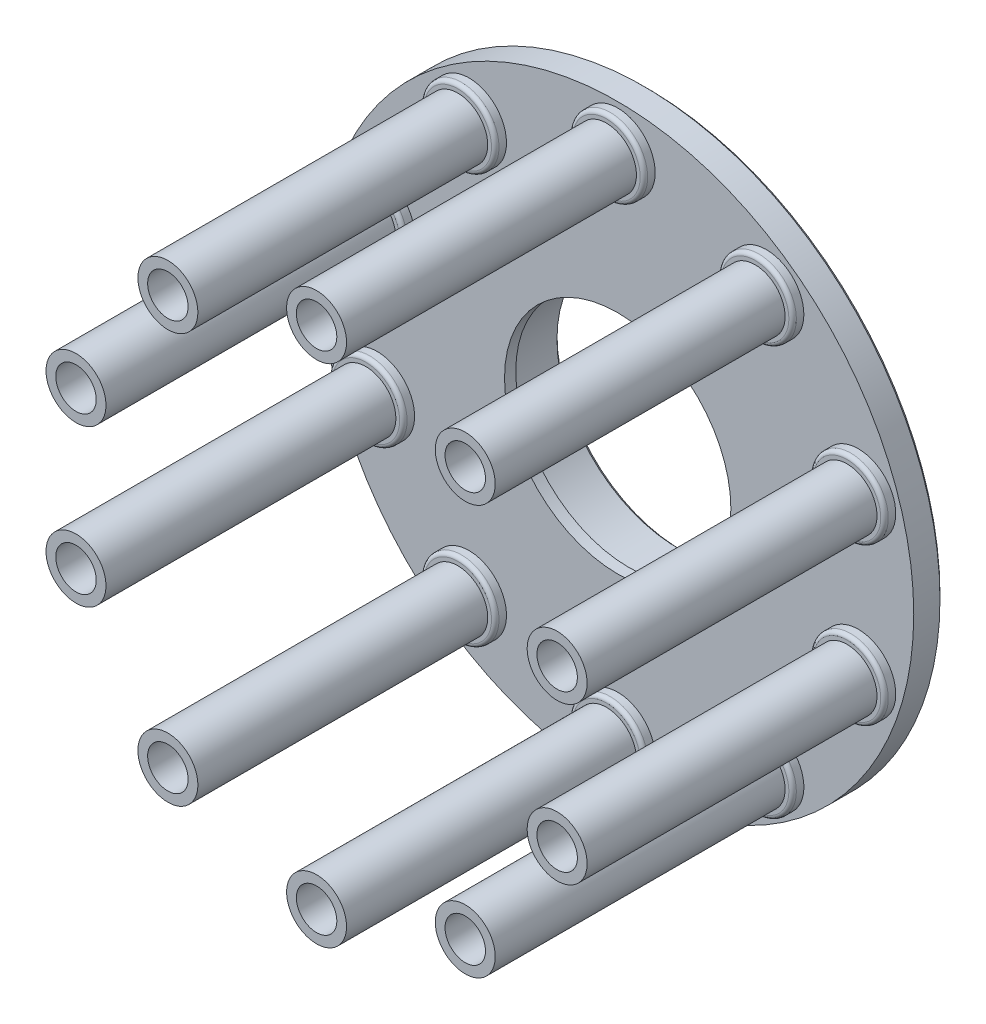
SolidWorks part; units mm, degrees
material "PLA"
ref_plane "Front Plane" through (0, 0, 0) normal (0, 0, 1) x (1, 0, 0)
ref_plane "Top Plane" through (0, 0, 0) normal (0, 1, 0) x (1, 0, 0)
ref_plane "Right Plane" through (0, 0, 0) normal (1, 0, 0) x (0, 0, -1)
sketch "Sketch1" plane through (0, 0, 0) normal (0, 0, 1) x (1, 0, 0)
  circle A0 centre (0, 0) radius 39.5
  circle A1 centre (0, 0) radius 33.75 construction
  circle A2 centre (0, 33.75) radius 2.7
  circle A3 centre (32.0982, 10.4293) radius 2.7
  circle A78 centre (19.8378, -27.3043) radius 2.7
  circle A79 centre (0, 33.75) radius 4.25 construction
  circle A80 centre (0, 0) radius 38 construction
  circle A89 centre (-19.8378, -27.3043) radius 2.7
  circle A90 centre (-32.0982, 10.4293) radius 2.7
  point P15 (0, 0)
  dimension "D2" = 67.5
  dimension "D3" = 5.4
  dimension "D5" = 8.5
  dimension "D4" = 5
extrude "Boss-Extrude1" add sketch "Sketch1" along normal blind 4
sketch "Sketch2" plane through (0, 0, 4) normal (0, 0, 1) x (1, 0, 0)
  circle A0 centre (0, 33.75) radius 4
  circle A2 centre (0, 33.75) radius 2.7 construction
  circle A5 centre (0, 33.75) radius 2.7
  point P15 (0, 0)
  dimension "D1" = 8
extrude "Boss-Extrude2" add sketch "Sketch2" along normal blind 40.176
sketch "Sketch3" plane through (0, 0, 4) normal (0, 0, 1) x (1, 0, 0)
  arc A2 (5, 33.75) -> (5, 33.75) centre (0, 33.75) ccw
  circle A3 centre (0, 33.75) radius 5
  circle M5 centre (0, 33.75) radius 4
extrude "Boss-Extrude3" add sketch "Sketch3" along normal blind 1.5 contours A3 M5 region at (-4.8586, 33.75, 4)
sketch "Sketch4" plane through (0, 0, 4) normal (0, 0, 1) x (1, 0, 0)
  line L0 (0, 0) -> (-23.2175, 31.9562) construction
  line L1 (0, 0) -> (0, 33.75) construction
  circle A0 centre (0, 0) radius 39.5 construction
  circle A1 centre (0, 0) radius 39.5
  circle A2 centre (0, 33.75) radius 13.75 construction
  circle A6 centre (0, 0) radius 33.75 construction
  arc A8 (-14.9918, 36.5444) -> (-10.4983, 22.6889) centre (0, 33.75) ccw
  circle A9 centre (0, 0) radius 25
  circle A11 centre (0, 0) radius 20 construction
  arc A13 (-30.1231, 25.5509) -> (-18.3343, 16.9957) centre (-32.0982, 10.4293) cw
  circle A16 centre (0, 33.75) radius 15.25 construction
  point P15 (0, 0)
  point P25 (0, 0)
  dimension "D4" = 5
  dimension "D1" = 27.5
  dimension "D5" = 40
  dimension "D2" = 36
  dimension "D3" = 1.5
extrude "Boss-Extrude4" [suppressed] add sketch "Sketch4" along normal blind 40.176 contours A1 A13 A9 A8
sketch "Sketch12" [suppressed] plane through (0, 0, 37.8382) normal (0, 0, 1) x (1, 0, 0)
  arc A0 (-11.2345, 15.816) -> (-15.816, 11.2345) centre (0, 0) ccw construction
  arc A1 (-11.2345, 15.816) -> (-15.816, 11.2345) centre (0, 0) ccw
  dimension "D1" = 6.4791
fillet "Fillet2" radius 0.5 1 edges at (5, 33.75, 5.5)
fillet "Fillet5" [suppressed] radius 1.6198
pattern_circular "CirPattern1" count 10 over 360 about axis through (0, 0, 4) along (0, 0, -1) of "Fillet2", "Boss-Extrude3", "Boss-Extrude2" reverse direction yes
ref_plane "Plane1" through (0, 0, 44.176) normal (0, 0, 1) x (1, 0, 0)
chamfer "Chamfer1" distance 0.5 angle 45 1 edges at (39.5, 0, 0)
sketch "Sketch9" plane through (0, 0, 4) normal (0, 0, 1) x (1, 0, 0)
  circle A0 centre (0, 0) radius 8
  dimension "D1" = 16
extrude "Cut-Extrude4" cut sketch "Sketch9" against normal through all
sketch "Sketch10" plane through (0, 0, 0) normal (0, 0, -1) x (-1, 0, 0)
  circle A0 centre (0, 0) radius 8 construction
  circle A1 centre (0, 0) radius 8
  circle A2 centre (0, 0) radius 6.5
extrude "Boss-Extrude7" add sketch "Sketch10" against normal blind 6.5
sketch "Sketch13" plane through (0, 0, 0) normal (0, 1, 0) x (1, 0, 0)
  line L0 (0, 0) -> (0, -44.176) construction
  line L1 (-4, -44.176) -> (4, -44.176) construction
  line L2 (17.1378, -4) -> (22.5378, -4) construction
  line L3 (-37.5, 0.5) -> (-47.5, -4) construction
  line L4 (-43.8447, -4) -> (-34.9558, 0)
  line L7 (39, 0) -> (-39, 0) construction
  line L8 (0, -4) -> (-47.5, -4) construction
  line L9 (-34.9558, 0) -> (-43.8447, 0)
  line L10 (-43.8447, 0) -> (-43.8447, -4)
  dimension "D1" = 37.5
  dimension "D2" = 47.5
  dimension "D3" = 4.5
  dimension "D4" = 1.5
sketch "Sketch14" plane through (0, 0, 4) normal (0, 0, 1) x (1, 0, 0)
  circle A0 centre (0, 0) radius 16.1
  circle A1 centre (0, 0) radius 6.5 construction
  dimension "D1" = 32.2
extrude "Cut-Extrude5" cut sketch "Sketch14" against normal through all both and the other way through all
sketch "Sketch15" plane through (0, 0, 4) normal (0, 0, 1) x (1, 0, 0)
  circle A0 centre (0, 0) radius 16.1
  circle A1 centre (0, 0) radius 15.1
  circle A2 centre (0, 0) radius 16.1 construction
  dimension "D1" = 1
extrude "Boss-Extrude8" add sketch "Sketch15" against normal blind 1.5
sketch "Sketch16" plane through (0, 0, 0) normal (0, 0, -1) x (-1, 0, 0)
  circle A0 centre (0, 0) radius 18.1
  circle A1 centre (0, 0) radius 16.1 construction
  circle M1 centre (0, 0) radius 16.1
extrude "Boss-Extrude9" add sketch "Sketch16" along normal blind 4.5 contours A0 M1 region at (17.5881, 0, 0)
chamfer "Chamfer3" distance 2 distance2 4.5 1 edges at (18.1, 0, 0) first distance on face at (18.1, 0, 0)
sketch "Sketch5" [suppressed] plane through (0, 0, 32.8234) normal (0, 0, 1) x (1, 0, 0)
  line L0 (0, 0) -> (-22.4506, 22.4506) construction
  line L1 (0, 0) -> (0, 26) construction
  circle A3 centre (-19.6222, 19.6222) radius 1.7
  circle A4 centre (0, 0) radius 31.75 construction
  arc A5 (-13.189, 28.881) -> (-28.881, 13.189) centre (0, 0) ccw construction
  dimension "D2" = 3.4
  dimension "D1" = 4
  dimension "D3" = 36
extrude "Cut-Extrude1" [suppressed] cut sketch "Sketch5" against normal through all
sketch "Sketch7" plane through (0, 0, 0) normal (0, 0, -1) x (-1, 0, 0)
  circle A0 centre (0, 33.75) radius 4.45
  circle A1 centre (0, 0) radius 33.75 construction
  point P15 (0, 0)
  dimension "D1" = 8.9
extrude "Cut-Extrude3" cut sketch "Sketch7" against normal blind 5 and the other way through all
sketch "Sketch6" [suppressed] plane through (0, 0, 0) normal (0, 0, -1) x (-1, 0, 0)
  circle A0 centre (19.6222, 19.6222) radius 2.95
  dimension "D1" = 5.9
extrude "Cut-Extrude2" [suppressed] cut sketch "Sketch6" against normal blind 3 and the other way through all
pattern_circular "CirPattern2" count 10 over 360 about axis through (0, 0, 4) along (0, 0, -1) of "Cut-Extrude3" reverse direction yes
chamfer "Chamfer4" distance 0.5 angle 45 1 edges at (-16.1, 0, -4.5)
equation "\"Nr_s\" = 170"
equation "\"module\" = 0.5"
equation "\"pressure_angle\" = 20.0"
equation "\"h_a\" = 0.5"
equation "\"h_f\" = 0.625"
equation "\"clr_tip_root\" = 0.125"
equation "\"dp_r_s\" = 85.0"
equation "\"db_r\"= \"dp_r_s\" * cos ( \"pressure_angle\" )'base CD"
equation "\"bearing_ID\" = 75"
equation "\"bearing_OD\" = 95"
equation "\"bearing_height\" = 10"
equation "\"clearance_planet\" = 1.5"
equation "\"case_dist\" = 6.5"
equation "\"Motor_case_OD_max\" = 131.3"
equation "\"case_mounting_PCD\" = 123.8"
equation "\"bearing mount thickness\" = 8"
equation "\"case_mounting_hole_dia\" = 3"
equation "\"output_mounting_PCD\" = 103"
equation "\"output_mounting_hole_dia\" = 4"
equation "\"clearance_case_mount_holes_shell_thickness\" = 1"
equation "\"motor_case_OD_base\" = 121.8"
equation "\"sec_carrier_thickness\" = 5"
equation "\"sun_coupler_hub_thickness\" = 4"
equation "\"clearance_sun_coupler_sec_carrier\" = 1.5"
equation "\"clearance_motor_and_case\" = 5"
equation "\"motor_OD\" = 106.8"
equation "\"Motor_case_thickness\" = 2.5"
equation "\"Motor_case_ID\" = 116.8"
equation "\"case_mounting_hole_shift\" = 1.0"
equation "\"output_mounting_nut_wrench_size\" = 7"
equation "\"output_mounting_nut_thickness\" = 3.2"
equation "\"case_mounting_hole_allen_socket_dia\" = 5.5"
equation "\"output_mounting_nut_depth\" = 3"
equation "\"case_mounting_bolt_depth\" = 4.5"
equation "\"Ns\" = 80"
equation "\"Np_b\" = 55"
equation "\"ring_radial_thickness\" = 5"
equation "\"ring_OD\"= \"Nr_s\" * \"module\" + \"ring_radial_thickness\" * 2"
equation "\"ring_to_chamfer_clearance\" = 1.5"
equation "\"Motor_case_OD_base_to_chamfer\" = 5"
equation "\"pattern_offset_from_motor_case_OD_base\" = 3"
equation "\"pattern_bulge_dia\" = 3"
equation "\"pattern_num_bulge\" = 18"
equation "\"pattern_depth\" = 2"
equation "\"motor_height\" = 47.6"
equation "\"case_mounting_wrench_size\" = 5.5"
equation "\"case_mounting_nut_clearance\" = 2"
equation "\"base_plate_thickness\" = 4"
equation "\"case_mounting_nut_thickness\" = 2.4"
equation "\"case_mounting_surface_height\" = 4"
equation "\"motor_mount_hole_PCD\" = 40"
equation "\"motor_mount_hole_dia\" = 5"
equation "\"motor_mount_hole_num\" = 4"
equation "\"central_hole_offset_from_motor_mount_PCD\" = 5"
equation "\"wire_slot_dist_from_center\" = 45.5"
equation "\"wire_slot_length\" = 10"
equation "\"wire_slot_radius\" = 3"
equation "\"driver_upper_holes_dist_from_center\" = 29"
equation "\"driver_lower_holes_dist_from_center\" = 13"
equation "\"driver_side_holes_dist_from_center\" = 22.5"
equation "\"driver_mount_holes_dia\" = 3"
equation "\"driver_mount_inserts_OD\" = 4.8"
equation "\"driver_mount_thickness\" = 1.5"
equation "\"driver_mount_height\" = 6"
equation "\"air_flow_hole_offset\" = 3"
equation "\"num_planet\" = 5"
equation "\"planet_pin_bolt_dia\" = 5"
equation "\"planet_pin_socket_head_dia\" = 8.5"
equation "\"carrier_PCD\" = 67.5"
equation "\"D2@Sketch1\"=\"carrier_PCD\""
equation "\"D3@Sketch1\"=\"planet_pin_bolt_dia\" + \"tight_clearance_3DP\""
equation "\"D4@Sketch1\"=\"num_planet\""
equation "\"D1@Boss-Extrude2\" = \"fw_p_s\" + \"clearance_planet\" * 2 + \"fw_p_b\""
equation "\"D1@Boss-Extrude3\"=\"clearance_planet\""
equation "\"D1@Sketch4\"=\"Np_b\"*\"module\""
equation "\"D3@Sketch4\"=\"clearance_planet\""
equation "\"D1@Boss-Extrude4\" = \"fw_p_s\" + \"clearance_planet\" * 2 + \"fw_p_b\""
equation "\"D1@Fillet2\"=\"clearance_planet\"/3"
equation "\"D1@CirPattern1\"=2*\"num_planet\""
equation "\"D1@CirPattern2\"=2*\"num_planet\""
equation "\"D1@Boss-Extrude7\"=\"bearing_height\"+ \"carrier_bearing_step_width\" - \"sun_shaft_bearing_width\""
equation "\"planet_shaft_dia\" = 8"
equation "\"D1@Sketch2\"= \"planet_shaft_dia\""
equation "\"planet_shaft_step_offset\" = 1"
equation "\"D1@Sketch3\"=\"planet_shaft_step_offset\""
equation "\"carrier_trapezoidal_support_sun_offset\" = 5"
equation "\"D4@Sketch4\"=\"carrier_trapezoidal_support_sun_offset\""
equation "\"carrier_trapezoidal_support_hole_PCD_offset_bearing_ID\" = 4"
equation "\"carrier_trapezoidal_support_hole_dia\" = 3"
equation "\"D2@Sketch5\"=\"carrier_trapezoidal_support_hole_dia\" + \"tight_clearance_3DP\""
equation "\"D1@Cut-Extrude2\"=\"carrier_trapezoidal_support_hole_dia\""
equation "\"carrier_trapezoidal_support_hole_socket_head_dia\" = 5.5"
equation "\"D1@Sketch6\"=\"carrier_trapezoidal_support_hole_socket_head_dia\" +  \"tight_clearance_3DP\""
equation "\"D1@Cut-Extrude3\"=\"planet_pin_bolt_dia\""
equation "\"D1@Sketch7\"=\"planet_pin_socket_head_dia\" + \"tight_clearance_3DP\""
equation "\"carrier_bearing_step_width\" = 1.5"
equation "\"standard_clearance_1_5mm\" = 1.5"
equation "\"standard_fillet_1_5mm\" = 1.5"
equation "\"sun_shaft_bearing_OD\" = 16"
equation "\"D1@Sketch9\"=\"sun_shaft_bearing_OD\""
equation "\"D1@Sketch10\"=\"standard_clearance_1_5mm\""
equation "\"sun_shaft_bearing_width\" = 5"
equation "\"standard_bearing_insertion_chamfer\" = 0.5"
equation "\"D1@Chamfer1\"=\"standard_bearing_insertion_chamfer\""
equation "\"D5@Sketch4\"=\"Ns\"*\"module\""
equation "\"D1@Sketch5\"=\"carrier_trapezoidal_support_hole_PCD_offset_bearing_ID\""
equation "\"D1@Plane1\" = \"fw_p_s\" + \"clearance_planet\" * 2 + \"fw_p_b\""
equation "\"D2@Sketch4\"=180/\"num_planet\""
equation "\"D3@Sketch5\"=180/\"num_planet\""
equation "\"carrier_trapezoidal_support_hole_wrench_size\" = 5.5"
equation "\"planet_pin_bolt_wrench_size\" = 8"
equation "\"pressure angle\" = 20.0"
equation "\"h_b\" = 0.625"
equation "\"dp_s\" = 40.0"
equation "\"db_s\" = 37.58770483143634"
equation "\"fw_s_calc\" = 4.872946430626146"
equation "\"alpha_s\" = 0.8539582918412272"
equation "\"beta_s\" = 0.5420834163175456"
equation "\"dp_p_b\" = 27.5"
equation "\"db_p_b\" = 25.84154707161248"
equation "\"fw_p_s\" = 15.81085678360617"
equation "\"alpha_p_b\" = 0.8539582918412449"
equation "\"beta_p_b\" = 1.564810689044783"
equation "\"planet_bearing_OD\" = 12"
equation "\"planet_bearing_width\" = 3.5"
equation "\"planet_bore\" = 10"
equation "\"motor_output_hole_PCD\" = 23"
equation "\"motor_output_hole_dia\" = 4"
equation "\"motor_output_hole_num\" = 4"
equation "\"sun_shaft_bearing_ID\" = 8"
equation "\"sun_hub_dia\" = 30.0"
equation "\"sun_central_bolt_dia\" = 5"
equation "\"sun_central_bolt_socket_head_dia\" = 8.5"
equation "\"fw_s_used\" = 44.67596466627659"
equation "\"motor_output_hole_CSK_OD\" = 8"
equation "\"motor_output_hole_CSK_head_height\" = 2.0"
equation "\"bearing_retainer_thickness\" = 2"
equation "\"Np_s\" = 35"
equation "\"fw_p_b\" = 21.365107882670422"
equation "\"dp_p_s\" = 17.5"
equation "\"db_p_s\" = 16.444620863753396"
equation "\"alpha_p_s\" = 0.8539582918412556"
equation "\"beta_p_s\" = 3.434940559174632"
equation "\"D1@Fillet5\"= \"D1@Sketch12\" / 4"
equation "\"Nr_b\" = 190"
equation "\"dp_r_b\" = 95.0"
equation "\"db_r_b\" = 89.2707989746613"
equation "\"fw_r_b\" = 21.365107882670422"
equation "\"alpha_r_b\" = 0.8539582918412414"
equation "\"beta_r_b\" = 2.655285004735114"
equation "\"ring_OD_b\" = 105.0"
equation "\"Fillet10\"= IIF ( \"ring_OD_b\" > ( \"bearing_OD\" + 2 * \"bearing mount thickness\" ) , \"suppressed\" , \"unsuppressed\" )"
equation "\"Fillet11\"= IIF ( \"ring_OD_b\" < ( \"bearing_OD\" + 2 * \"bearing mount thickness\" ) , \"suppressed\" , \"unsuppressed\" )"
equation "\"clr_tip_root_s\" = 0.125"
equation "\"db_r_s\" = 79.87387276680222"
equation "\"fw_r_s\" = 14.31085678360617"
equation "\"alpha_r_s\" = 0.8539582918412307"
equation "\"beta_r_s\" = 2.766740113094226"
equation "\"D1@Sketch13\"=\"bearing_ID\"/2"
equation "\"D2@Sketch13\"=(\"Nr_s\"*\"module\"+\"ring_radial_thickness\"*2)*0.5"
equation "\"D3@Sketch13\"=\"standard_clearance_1_5mm\"*3"
equation "\"D4@Sketch13\"=\"standard_clearance_1_5mm\""
equation "\"D5@Sketch1\"=\"planet_pin_socket_head_dia\""
equation "\"D1@Sketch1\"=\"standard_clearance_1_5mm\""
equation "\"small_ring_case_thickness\" = 4"
equation "\"carrier_thickness\" = 4"
equation "\"small_ring_output_wall_thickness\" = 5"
equation "\"small_ring_output_wall_to_bearing_shaft_attachement_hole_dia\" = 4"
equation "\"small_ring_output_wall_to_bearing_shaft_attachement_hole_depth\" = 6.5"
equation "\"small_ring_output_wall_to_bearing_shaft_attachement_nut_wrench\" = 7"
equation "\"small_ring_output_wall_to_bearing_shaft_attachement_nut_thickness\" = 3.2"
equation "\"small_ring_output_wall_to_bearing_shaft_attachement_hole_pcd\" = 12"
equation "\"small_ring_output_wall_to_bearing_shaft_attachement_hole_num\" = 3"
equation "\"small_ring_output_wall_to_bearing_shaft_attachement_hole_CSK_OD\" = 8"
equation "\"small_ring_output_wall_to_bearing_shaft_attachement_hole_CSK_head_height\" = 2.0"
equation "\"carrier_small_ring_inner_bearing_ID\" = 20"
equation "\"carrier_small_ring_inner_bearing_OD\" = 32"
equation "\"carrier_small_ring_inner_bearing_height\" = 7"
equation "\"carrier_small_ring_inner_bearing_flap\" = 2"
equation "\"gear_casing_big_ring_to_bearing_dist\" = 24.81085678360617"
equation "\"gear_casing_thickness\" = 4"
equation "\"D1@Boss-Extrude1\"=\"carrier_thickness\""
equation "\"D1@Boss-Extrude9\"= \"carrier_small_ring_inner_bearing_height\" - \"carrier_thickness\" + \"standard_clearance_1_5mm\""
equation "\"D3@Chamfer3\"=\"carrier_small_ring_inner_bearing_height\"-\"carrier_thickness\" + \"standard_clearance_1_5mm\""
equation "\"D1@Chamfer3\"=\"standard_clearance_1_5mm\"*4/3"
equation "\"D1@Sketch14\"=\"carrier_small_ring_inner_bearing_OD\" + \"tight_clearance_3DP\"/2"
equation "\"D1@Sketch16\"=\"standard_clearance_1_5mm\"*4/3"
equation "\"tight_clearance_3DP\" = 0.4"
equation "\"loose_clearance_3DP\" = 0.8"
equation "\"D1@Chamfer4\"= \"standard_bearing_insertion_chamfer\""
